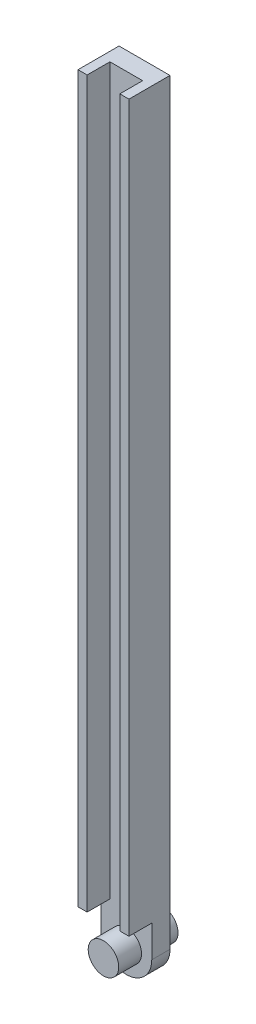
SolidWorks part; units mm, degrees
note: The reader was unsure of these and kept them because the rebuilt part matched: shared geometry of "Sketch1<4>".
ref_plane "Front Plane" through (0, 0, 0) normal (0, 0, 1) x (1, 0, 0)
ref_plane "Top Plane" through (0, 0, 0) normal (0, 1, 0) x (1, 0, 0)
ref_plane "Right Plane" through (0, 0, 0) normal (1, 0, 0) x (0, 0, -1)
sketch "Sketch1" plane through (0, 0, 0) normal (0, 0, 1) x (1, 0, 0)
  line L0 (-1300.1002, 1195.6457) -> (-1158.1954, 1195.6457)
  line L1 (-1158.1954, -911.7362) -> (-1158.1954, 1195.6457)
  line L2 (-1300.1002, -911.7362) -> (-1300.1002, 1195.6457)
  line L3 (-1300.1002, -823.1813) -> (-1274.7002, -823.1813)
  line L4 (-1274.7002, -823.1813) -> (-1274.7002, 1195.6457)
  line L5 (-1183.5954, -823.1813) -> (-1183.5954, 1195.6457)
  line L6 (-1274.7002, -911.7362) -> (-1274.7002, 1195.6457) construction
  line L7 (-1183.5954, -911.7362) -> (-1183.5954, 1195.6457) construction
  line L8 (-1183.5954, -823.1813) -> (-1158.1954, -823.1813)
  circle A0 centre (-1229.1478, -911.7362) radius 42.5148
  arc A1 (-1300.1002, -911.7362) -> (-1158.1954, -911.7362) centre (-1229.1478, -911.7362) ccw
  dimension "D1" = 25.4
  dimension "D2" = 25.4
extrude "Extrude1" add sketch "Sketch1" along normal blind 50.8 contours L2 A1 L1 L8 L5 L0 L4 L3 A0
extrude "Extrude2" add sketch "Sketch1<4>" along normal blind 114.3 contours L3 L4 L0 L2 | L5 L8 L1 L0
sketch "Sketch1<4>" plane through (0, 0, 0) normal (0, 0, 1) x (1, 0, 0) same geometry as "Sketch1"
sketch "Sketch2" plane through (0, 0, 0) normal (0, 0, -1) x (-1, 0, 0)
  circle A0 centre (1229.1478, -911.7362) radius 42.5148
extrude "Extrude3" add sketch "Sketch2" against normal up to surface (165.1 mm away) from offset 50.8 up to face at (-1170.8954, 186.2322, 114.3)
